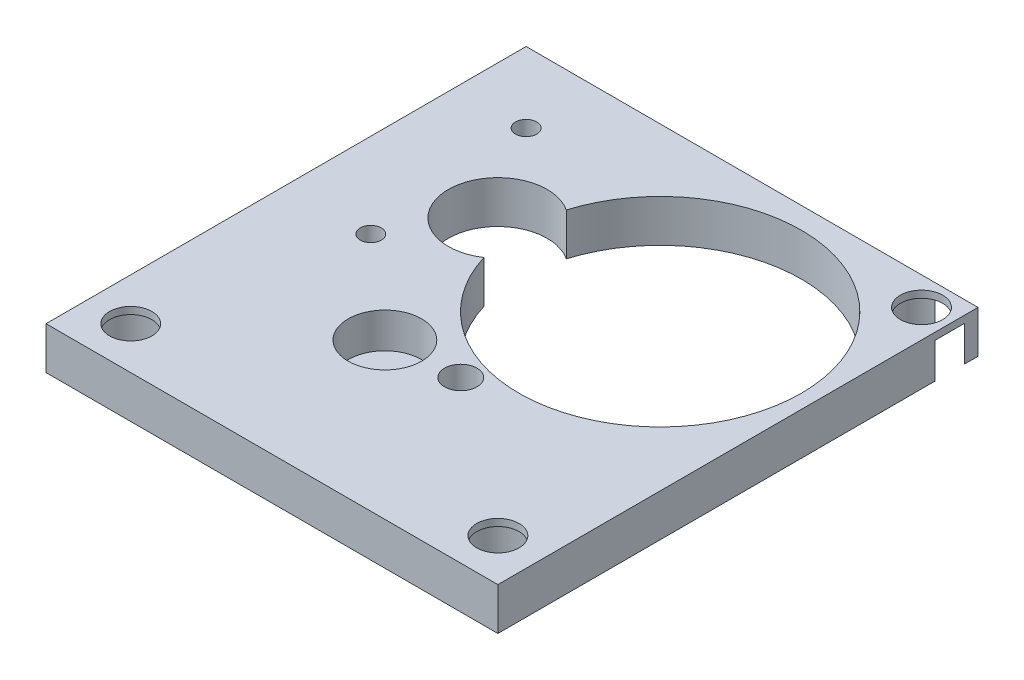
SolidWorks part; units mm, degrees
note: The reader was unsure of these and kept them because the rebuilt part matched: shared geometry of "草图1<28>", "草图2<3>", "草图1<29>".
ref_plane "前视基准面" through (0, 0, 0) normal (0, 0, 1) x (1, 0, 0)
ref_plane "上视基准面" through (0, 0, 0) normal (0, 1, 0) x (1, 0, 0)
ref_plane "右视基准面" through (0, 0, 0) normal (1, 0, 0) x (0, 0, -1)
other "Configuration Table"
sketch "草图1" plane through (0, 0, 0) normal (0, 1, 0) x (1, 0, 0)
  line L5 (-13, 23) -> (19, 23)
  line L6 (-13, 23) -> (-13, -11)
  line L7 (-13, -11) -> (19, -11)
  line L8 (19, 23) -> (19, -11)
  circle A0 centre (11.4735, 0) radius 3.3882
  circle A1 centre (-3.4891, 11.4815) radius 1.15
  circle A2 centre (8.0109, 11.4815) radius 1.15
  circle A4 centre (-3.4891, 11.4815) radius 8.5
  circle A5 centre (8.0109, 11.4815) radius 10
  circle A7 centre (4.985, 0.3868) radius 10
  circle A8 centre (4.985, 0.3868) radius 1.15
  circle A9 centre (0, 0) radius 5.5
  circle A10 centre (0, 0) radius 2.6
  circle A11 centre (-3.4891, 11.4815) radius 3.5
  dimension "D2" = 2.3
  dimension "D3" = 2.3
  dimension "D4" = 11.5
  dimension "D5" = 2.3
  dimension "D6" = 11.5
  dimension "D7" = 5.2
  dimension "D10" = 17
  dimension "D11" = 20
  dimension "D12" = 14
  dimension "D13" = 20
  dimension "D15" = 7
  dimension "D8" = 11
  dimension "D9" = 12
  dimension "D14" = 6.5
  dimension "D16" = 5
  dimension "D17" = 23
  dimension "D18" = 19
  dimension "D19" = 13
  dimension "D20" = 11
extrude "凸台-拉伸1" add sketch "草图1" along normal blind 2.5 contours L8 L7 L6 L5 | A10 | A11 | A5
extrude "凸台-拉伸2" add sketch "草图1<28>" against normal blind 0.5 contours L6 L7 L8 L5 | A11 | A5
sketch "草图1<28>" plane through (0, 0, 0) normal (0, 1, 0) x (1, 0, 0) same geometry as "草图1"
sketch "草图2" plane through (0, -0.5, 0) normal (0, -1, 0) x (1, 0, 0)
  circle A0 centre (17, -21) radius 1.5
  circle A1 centre (-10, 8) radius 1.5
  circle A2 centre (16, 8) radius 1.5
  circle A3 centre (17, -21) radius 2.25
  circle A4 centre (-10, 8) radius 2.25
  circle A5 centre (16, 8) radius 2.25
  dimension "D1" = 3
  dimension "D2" = 4.5
extrude "切除-拉伸1" cut sketch "草图2" against normal through all contours A0 | A2 | A1
extrude "切除-拉伸2" cut sketch "草图2<3>" against normal blind 2.5 contours A5 | A4 | A3
sketch "草图2<3>" plane through (0, -0.5, 0) normal (0, -1, 0) x (1, 0, 0) same geometry as "草图2"
sketch "草图3" plane through (0, -0.5, 0) normal (0, -1, 0) x (1, 0, 0)
  line L0 (-13, -23) -> (15.9692, -23) construction
  line L1 (-13, -23) -> (-13, 11) construction
  circle A0 centre (-7, -6) radius 0.75
  circle A1 centre (-8, -18) radius 0.75
  point P8 (-13, -6)
  dimension "D1" = 1.5
  dimension "D2" = 5
  dimension "D3" = 5
  dimension "D4" = 6
extrude "切除-拉伸3" cut sketch "草图3" against normal through all
extrude "切除-拉伸4" cut sketch "草图1<29>" against normal through all both and the other way through all contours A8
sketch "草图1<29>" plane through (0, 0, 0) normal (0, 1, 0) x (1, 0, 0) same geometry as "草图1"
